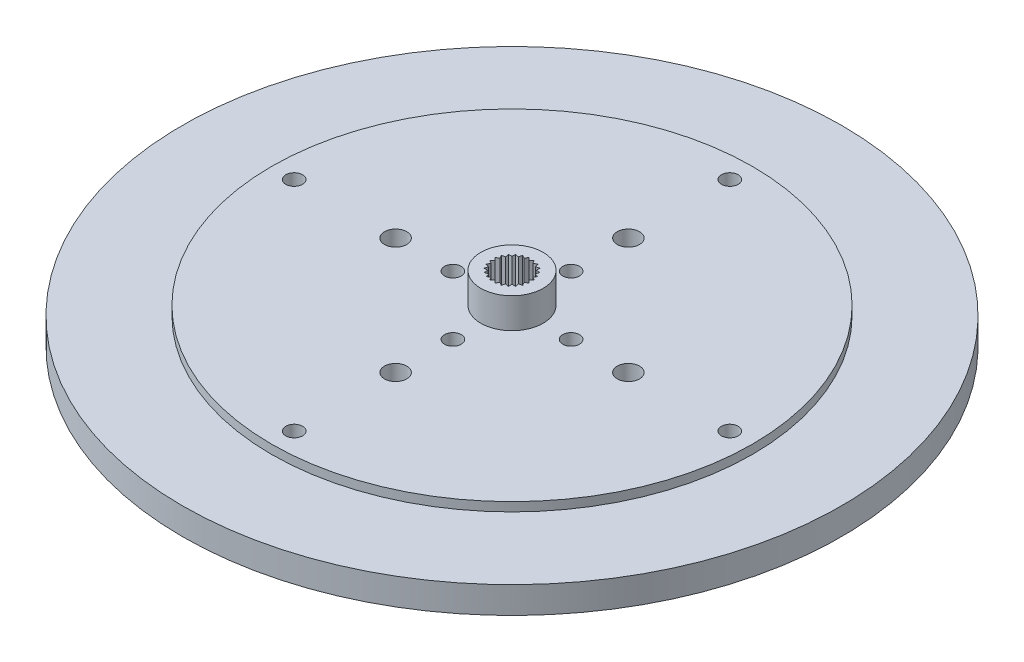
SolidWorks part; units mm, degrees
material "PE High Density"
ref_plane "Front Plane" through (0, 0, 0) normal (0, 0, 1) x (1, 0, 0)
ref_plane "Top Plane" through (0, 0, 0) normal (0, 1, 0) x (1, 0, 0)
ref_plane "Right Plane" through (0, 0, 0) normal (1, 0, 0) x (0, 0, -1)
sketch "Sketch1" plane through (0, 0, 0) normal (0, 1, 0) x (1, 0, 0)
  circle A0 centre (0, 0) radius 46.99
  dimension "D1" = 93.98
extrude "Extrude1" add sketch "Sketch1" along normal blind 3.81
sketch "Sketch2" plane through (0, 3.81, 0) normal (0, 1, 0) x (1, 0, 0)
  circle A0 centre (0, 0) radius 34.29
  dimension "D1" = 68.58
extrude "Extrude2" add sketch "Sketch2" along normal blind 1.27
sketch "Sketch3" plane through (0, 5.08, 0) normal (0, 1, 0) x (1, 0, 0)
  circle A0 centre (0, 0) radius 4.445
  dimension "D1" = 8.89
extrude "Extrude3" add sketch "Sketch3" along normal blind 4.318
sketch "Sketch4" plane through (0, 9.398, 0) normal (0, 1, 0) x (1, 0, 0)
  circle A0 centre (0, 0) radius 1.1811
  dimension "D1" = 2.3622
extrude "Extrude4" cut sketch "Sketch4" against normal through all
sketch "Sketch5" plane through (0, 5.08, 0) normal (0, 1, 0) x (1, 0, 0)
  line L0 (0, 0) -> (0, -8.4277) construction
  line L1 (0, -8.4277) -> (0, -16.5938) construction
  line L2 (0, -16.5938) -> (0, -31.0591) construction
  circle A0 centre (0, -8.4277) radius 1.1938
  circle A1 centre (0, -16.5938) radius 1.5875
  circle A2 centre (0, -31.0591) radius 1.1938
  dimension "D4" = 2.3876
  dimension "D5" = 3.175
  dimension "D1" = 14.4653
  dimension "D2" = 8.1661
  dimension "D3" = 8.4277
extrude "Extrude5" cut sketch "Sketch5" against normal through all
pattern_circular "CirPattern1" count 4 over 360 about axis through (0, 5.08, 0) along (0, 1, 0) of "Extrude5"
sketch "Sketch6" plane through (0, 9.398, 0) normal (0, 1, 0) x (1, 0, 0)
  circle A0 centre (0, 0) radius 2.8321
  dimension "D1" = 5.6642
extrude "Extrude6" cut sketch "Sketch6" against normal blind 4.318
sketch "Sketch7" plane through (0, 9.398, 0) normal (0, 1, 0) x (1, 0, 0)
  line L0 (0, 0) -> (0, 2.4384) construction
  line L1 (0, 0) -> (0.3697, 2.8079) construction
  line L2 (0, 0) -> (-0.3697, 2.8079) construction
  line L3 (0, 2.4384) -> (0.3697, 2.8079)
  line L4 (0, 2.4384) -> (-0.3697, 2.8079)
  line L5 (-0.3697, 2.8079) -> (-0.3697, 3.1029)
  line L6 (-0.3697, 3.1029) -> (0.3697, 3.1029)
  line L7 (0.3697, 3.1029) -> (0.3697, 2.8079)
  circle A0 centre (0, 0) radius 2.8321 construction
  dimension "D1" = 2.4384
  dimension "D2" = 7.5
  dimension "D3" = 7.5
extrude "Extrude7" add sketch "Sketch7" against normal up to surface (4.318 mm away) up to face at (0, 5.08, 2.8321)
pattern_circular "CirPattern2" count 24 over 360 about axis through (0, 5.08, 0) along (0, 1, 0) of "Extrude7"
ref_axis "Axis1" through (-31.0591, 0, 0) along (0, 1, 0)
ref_axis "Axis2" through (31.0591, 0, 0) along (0, 1, 0)
ref_plane "Plane1" through (0, 0, 0) normal (0, 0, 1) x (1, 0, 0)
